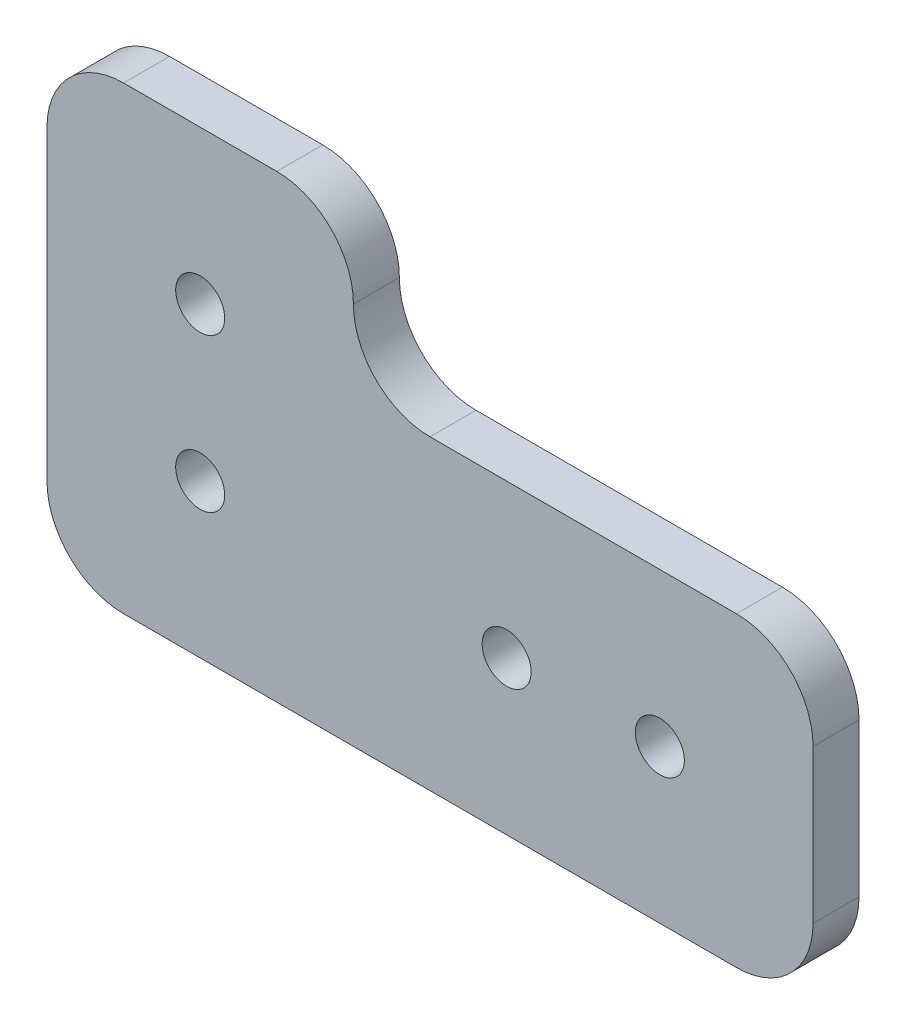
SolidWorks part; units mm, degrees
material "A-玻璃纤维"
ref_plane "前视基准面" through (0, 0, 0) normal (0, 0, 1) x (1, 0, 0)
ref_plane "上视基准面" through (0, 0, 0) normal (0, 1, 0) x (1, 0, 0)
ref_plane "右视基准面" through (0, 0, 0) normal (1, 0, 0) x (0, 0, -1)
sketch "草图1" plane through (0, 0, 0) normal (0, 0, 1) x (1, 0, 0)
  line L0 (0, 121.0618) -> (0, -112.0199) construction
  line L1 (233.0817, 0) -> (-238.105, 0) construction
  line L2 (0, 0) -> (0, 30)
  line L3 (0, 30) -> (20, 30)
  line L4 (20, 30) -> (20, 20)
  line L5 (20, 20) -> (50, 20)
  line L6 (50, 20) -> (50, 0)
  line L7 (50, 0) -> (0, 0)
  circle A0 centre (10, 20) radius 1.6
  circle A1 centre (10, 10) radius 1.6
  circle A2 centre (30, 10) radius 1.6
  circle A3 centre (40, 10) radius 1.6
  dimension "D4" = 10
  dimension "D5" = 30
  dimension "D6" = 10
  dimension "D7" = 3.2
  dimension "D8" = 10
  dimension "D9" = 10
  dimension "D11" = 10
  dimension "D1" = 20
  dimension "D2" = 20
  dimension "D10" = 10
extrude "凸台-拉伸1" add sketch "草图1" along normal blind 3
fillet "圆角1" radius 5 6 edges at (0, 0, 1.5) (50, 0, 1.5) (50, 20, 1.5) (20, 20, 1.5) (20, 30, 1.5) (0, 30, 1.5)
